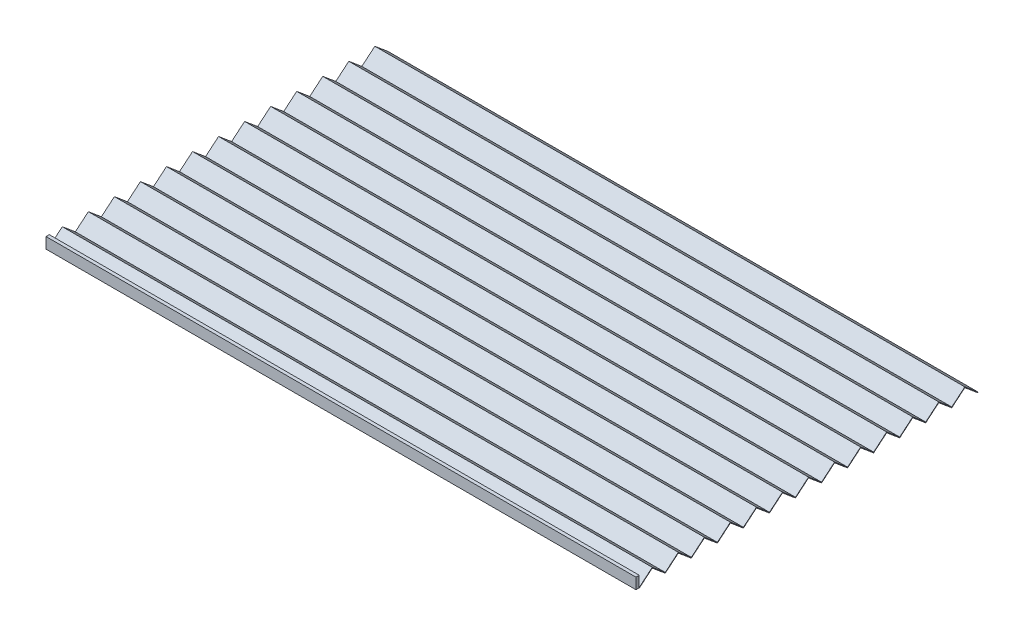
SolidWorks part; units mm, degrees
ref_plane "Front Plane" through (0, 0, 0) normal (0, 0, 1) x (1, 0, 0)
ref_plane "Top Plane" through (0, 0, 0) normal (0, 1, 0) x (1, 0, 0)
ref_plane "Right Plane" through (0, 0, 0) normal (1, 0, 0) x (0, 0, -1)
sketch "Sketch2" plane through (0, 0, 0) normal (0, 0, 1) x (1, 0, 0)
  line L1 (-270, 10) -> (270, 10)
  line L2 (-270, 10) -> (-270, 0)
  line L3 (-270, 0) -> (270, 0)
  line L4 (270, 10) -> (270, 0)
  point P4 (0, 0)
  dimension "D1" = 10
  dimension "D2" = 540
extrude "Boss-Extrude1" add sketch "Sketch2" along normal blind 3
sketch "Sketch3" plane through (270, 0, 0) normal (1, 0, 0) x (0, 0, -1)
  line L0 (0, 10) -> (309.9168, 10) construction
  line L1 (0, 0) -> (309.9168, 0) construction
  line L2 (309.9168, 10) -> (309.9168, 0) construction
  line L3 (0, 0) -> (11.9199, 10)
  line L4 (11.9199, 10) -> (23.8398, 0)
  line L5 (23.8398, 0) -> (35.7596, 10)
  line L6 (35.7596, 10) -> (47.6795, 0)
  line L7 (47.6795, 0) -> (59.5994, 10)
  line L8 (59.5994, 10) -> (71.5193, 0)
  line L9 (71.5193, 0) -> (83.4391, 10)
  line L10 (83.4391, 10) -> (95.359, 0)
  line L11 (95.359, 0) -> (107.2789, 10)
  line L12 (107.2789, 10) -> (119.1988, 0)
  line L13 (119.1988, 0) -> (131.1186, 10)
  line L14 (131.1186, 10) -> (143.0385, 0)
  line L15 (143.0385, 0) -> (154.9584, 10)
  line L16 (154.9584, 10) -> (166.8783, 0)
  line L17 (166.8783, 0) -> (178.7981, 10)
  line L18 (178.7981, 10) -> (190.718, 0)
  line L20 (190.718, 0) -> (202.6379, 10)
  line L21 (202.6379, 10) -> (214.5578, 0)
  line L22 (214.5578, 0) -> (226.4776, 10)
  line L23 (226.4776, 10) -> (238.3975, 0)
  line L24 (238.3975, 0) -> (250.3174, 10)
  line L25 (250.3174, 10) -> (262.2373, 0)
  line L26 (262.2373, 0) -> (274.1571, 10)
  line L27 (274.1571, 10) -> (286.077, 0)
  line L28 (286.077, 0) -> (297.9969, 10)
  line L29 (297.9969, 10) -> (309.9168, 0)
  line L30 (309.9168, 10) -> (309.9168, 0) construction
extrude "Extrude-Thin1" add sketch "Sketch3" against normal through all thin thin type mid plane wall 0.5
